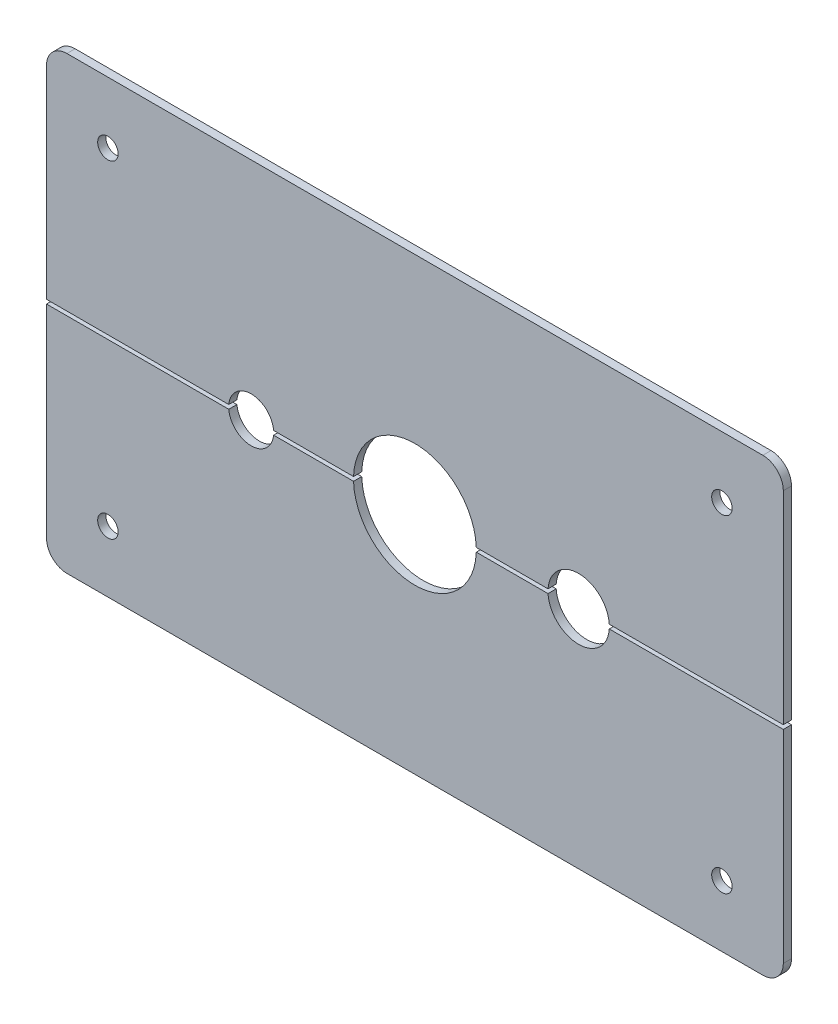
SolidWorks part; units mm, degrees
material "Q235-A"
ref_plane "前视基准面" through (0, 0, 0) normal (0, 0, 1) x (1, 0, 0)
ref_plane "上视基准面" through (0, 0, 0) normal (0, 1, 0) x (1, 0, 0)
ref_plane "右视基准面" through (0, 0, 0) normal (1, 0, 0) x (0, 0, -1)
sketch "草图1" plane through (0, 0, 0) normal (0, 0, 1) x (1, 0, 0)
  line L1 (90, -55) -> (-90, -55)
  line L2 (90, -55) -> (90, 55)
  line L3 (90, 55) -> (-90, 55)
  line L4 (-90, -55) -> (-90, 55)
  line L5 (90, -55) -> (-90, 55) construction
  line L6 (90, 55) -> (-90, -55) construction
  point P0 (0, 0)
  dimension "D1" = 110
  dimension "D2" = 180
base flange "基体-法兰1" sketch "草图1" thickness 2 reverse thickness direction no parameters "D1"=0.7366
sketch "草图6" plane through (0, 0, 0) normal (0, 0, 1) x (1, 0, 0)
  line L0 (-90, 0) -> (109.6511, 0) construction
  line L1 (-90, 55) -> (-90, -55) construction
  circle A0 centre (0, 0) radius 15
  circle A1 centre (-40, 0) radius 5.5
  circle A2 centre (40, 0) radius 7.5
  dimension "D1" = 30
  dimension "D2" = 11
  dimension "D3" = 15
  dimension "D4" = 40
  dimension "D5" = 40
extrude "切除-拉伸1" cut sketch "草图6" against normal blind 10 normal cut yes
fillet "圆角1" radius 5 4 edges at (90, 55, -1) (90, -55, -1) (-90, -55, -1) (-90, 55, -1)
sketch "草图7" plane through (0, 0, 0) normal (0, 0, 1) x (1, 0, 0)
  line L1 (-112.2398, -0.5) -> (112.2398, -0.5)
  line L2 (-112.2398, -0.5) -> (-112.2398, 0.5)
  line L3 (-112.2398, 0.5) -> (112.2398, 0.5)
  line L4 (112.2398, -0.5) -> (112.2398, 0.5)
  line L5 (-112.2398, -0.5) -> (112.2398, 0.5) construction
  line L6 (-112.2398, 0.5) -> (112.2398, -0.5) construction
  point P0 (0, 0)
  dimension "D1" = 1
extrude "切除-拉伸2" cut sketch "草图7" against normal blind 10 normal cut yes
sketch "草图8" plane through (0, 0, 0) normal (0, 0, 1) x (1, 0, 0)
  circle A0 centre (75, 40) radius 2.5
  circle A1 centre (-75, 40) radius 2.5
  circle A2 centre (-75, -40) radius 2.5
  circle A3 centre (75, -40) radius 2.5
  dimension "D1" = 150
  dimension "D4" = 75
  dimension "D5" = 5
  dimension "D2" = 80
  dimension "D3" = 40
extrude "切除-拉伸3" cut sketch "草图8" against normal blind 10
sketch "折弯-线1" [suppressed] plane through (0, 0, 0) normal (0, 1, 0) x (1, 0, 0)
sketch "边界框1" [suppressed] plane through (0, 0, 0) normal (0, 1, 0) x (1, 0, 0)
sheet metal parameters "钣金1" thickness 2 parameters "D1"=0.7366
flat pattern "平板型式1" [suppressed]
sketch "折弯-线2" plane through (0, 0, 0) normal (0, 1, 0) x (1, 0, 0)
sketch3d "边界框2" [suppressed]
  line L0 (-90, -60, 0) -> (90, -60, 0) construction
  line L1 (-90, 60, 0) -> (90, 60, 0) construction
  line L2 (-90, -60, 0) -> (-90, 60, 0) construction
  line L3 (90, -60, 0) -> (90, 60, 0) construction
sheet metal parameters "钣金2" thickness 2 parameters "D1"=0.7366
flat pattern "平板型式1"
sketch "折弯-线2" plane through (0, 0, 0) normal (0, 1, 0) x (1, 0, 0)
sketch3d "边界框2" [suppressed]
  line L0 (-90, 60, 0) -> (90, 60, 0) construction
  line L1 (-90, -60, 0) -> (90, -60, 0) construction
  line L2 (-90, 60, 0) -> (-90, -60, 0) construction
  line L3 (90, 60, 0) -> (90, -60, 0) construction
sheet metal parameters "钣金3" thickness 2 parameters "D1"=0.7366
flat pattern "平板型式3"
sketch "折弯-线3" plane through (0, 0, 0) normal (0, 1, 0) x (1, 0, 0)
sketch3d "边界框3" [suppressed]
  line L0 (-90, -0.5, 0) -> (90, -0.5, 0) construction
  line L1 (-90, -55, 0) -> (90, -55, 0) construction
  line L2 (-90, -0.5, 0) -> (-90, -55, 0) construction
  line L3 (90, -0.5, 0) -> (90, -55, 0) construction
sheet metal parameters "钣金4" thickness 2 parameters "D1"=0.7366
flat pattern "平板型式4"
sketch "折弯-线4" plane through (0, 0, 0) normal (0, 1, 0) x (1, 0, 0)
sketch "边界框4" [suppressed] plane through (0, 0, 0) normal (0, 1, 0) x (1, 0, 0)
sheet metal parameters "钣金5" thickness 2 parameters "D1"=0.7366
flat pattern "平板型式3"
sketch "折弯-线3" plane through (0, 0, 0) normal (0, 1, 0) x (1, 0, 0)
sketch3d "边界框3" [suppressed]
  line L0 (-90, -0.5, 0) -> (90, -0.5, 0) construction
  line L1 (-90, -55, 0) -> (90, -55, 0) construction
  line L2 (-90, -0.5, 0) -> (-90, -55, 0) construction
  line L3 (90, -0.5, 0) -> (90, -55, 0) construction
sheet metal parameters "钣金6" thickness 2 parameters "D1"=0.7366
flat pattern "平板型式4"
sketch "折弯-线4" plane through (0, 0, 0) normal (0, 1, 0) x (1, 0, 0)
sketch "边界框4" [suppressed] plane through (0, 0, 0) normal (0, 1, 0) x (1, 0, 0)
